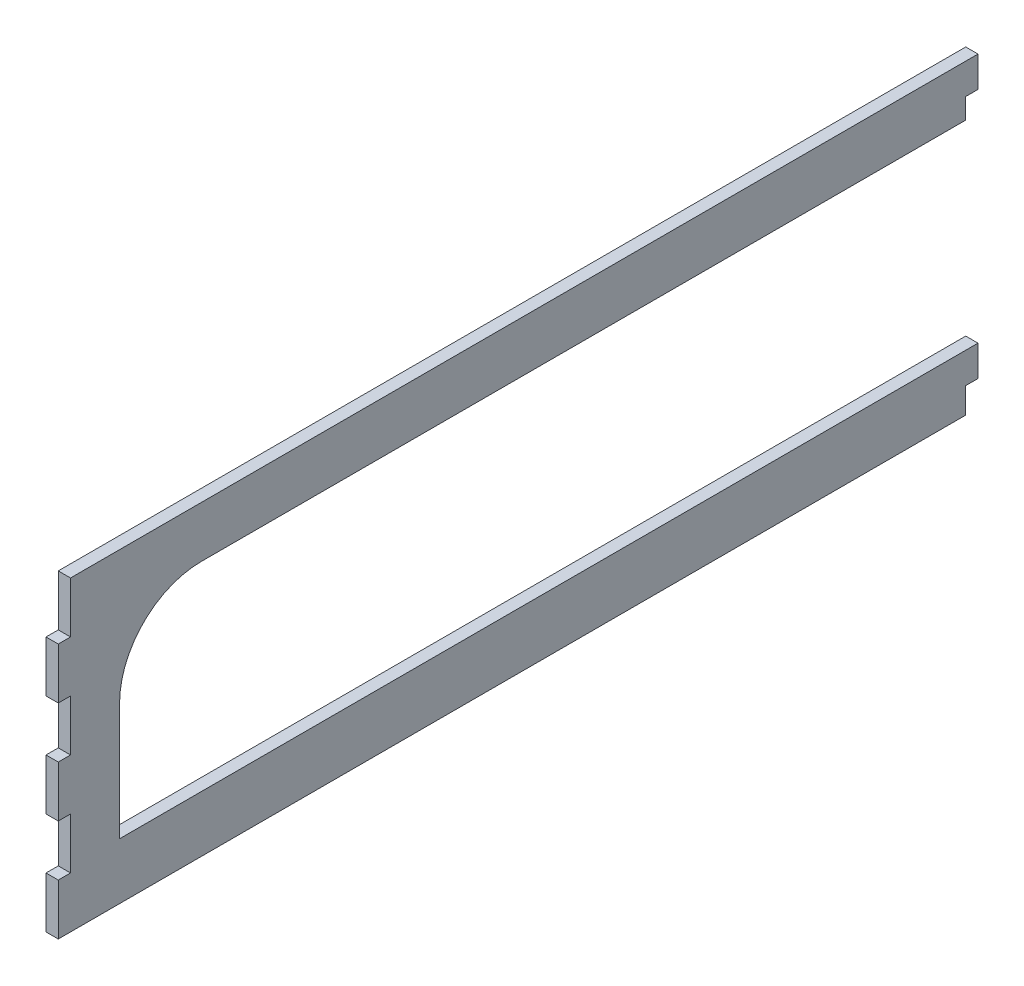
SolidWorks part; units mm, degrees
ref_plane "Front" through (0, 0, 0) normal (0, 0, 1) x (1, 0, 0)
ref_plane "Top" through (0, 0, 0) normal (0, 1, 0) x (1, 0, 0)
ref_plane "Right" through (0, 0, 0) normal (1, 0, 0) x (0, 0, -1)
sketch "Sketch1" plane through (0, 0, 0) normal (1, 0, 0) x (0, 0, -1)
  line L0 (450, 125) -> (450, 150)
  line L1 (0, 0) -> (450, 0)
  line L2 (0, 0) -> (0, 150)
  line L3 (0, 150) -> (450, 150)
  line L4 (450, 0) -> (450, 27.5)
  line L5 (450, 125) -> (30, 125)
  line L7 (450, 27.5) -> (30, 27.5)
  line L8 (30, 125) -> (30, 27.5)
  dimension "D1" = 420
  dimension "D2" = 150
  dimension "D3" = 27.5
  dimension "D4" = 25
  dimension "D5" = 30
extrude "Boss-Extrude1" add sketch "Sketch1" along normal blind 6
sketch "Sketch2" plane through (6, 0, 0) normal (1, 0, 0) x (0, 0, -1)
  line L1 (0, 150) -> (6, 150)
  line L2 (0, 150) -> (0, 125)
  line L3 (0, 125) -> (6, 125)
  line L4 (6, 150) -> (6, 125)
  dimension "D1" = 6
  dimension "D2" = 25
extrude "Cut-Extrude1" cut sketch "Sketch2" against normal blind 6
pattern_linear "LPattern1" count 3 spacing 50 along (0, -1, 0) of "Cut-Extrude1"
fillet "Fillet1" radius 40 1 edges at (3, 125, -30)
sketch "Sketch3" plane through (0, 0, 0) normal (-1, 0, 0) x (0, 0, 1)
  line L0 (-450, 0) -> (-450, 27.5) construction
  line L1 (-450, 135) -> (-444, 135)
  line L2 (-450, 135) -> (-450, 125)
  line L3 (-450, 125) -> (-444, 125)
  line L4 (-444, 135) -> (-444, 125)
  line L5 (-70, 125) -> (-450, 125) construction
  line L7 (-450, 12.5) -> (-444, 12.5)
  line L8 (-450, 12.5) -> (-450, 0)
  line L9 (-450, 0) -> (-444, 0)
  line L10 (-444, 12.5) -> (-444, 0)
  line L11 (0, 0) -> (-450, 0) construction
  line L12 (-450, 125) -> (-450, 150) construction
  point P4 (-450, 10.7307)
  point P13 (-450, 135)
  dimension "D1" = 6
  dimension "D2" = 10
  dimension "D3" = 12.5
extrude "Cut-Extrude2" cut sketch "Sketch3" against normal through all
